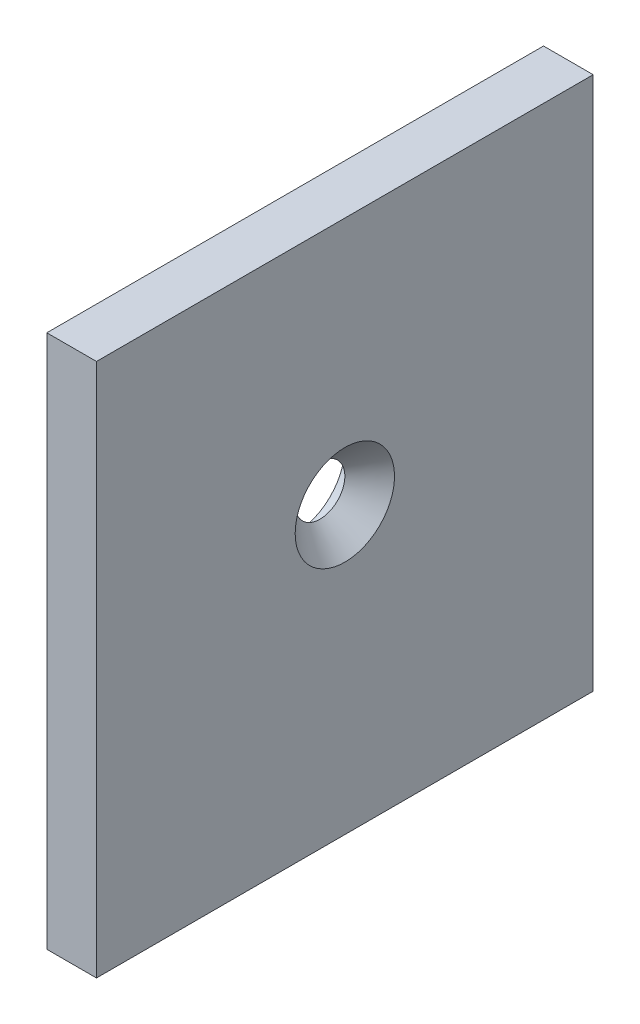
SolidWorks part; units mm, degrees
ref_plane "Plan de face" through (0, 0, 0) normal (0, 0, 1) x (1, 0, 0)
ref_plane "Plan de dessus" through (0, 0, 0) normal (0, 1, 0) x (1, 0, 0)
ref_plane "Plan de droite" through (0, 0, 0) normal (1, 0, 0) x (0, 0, -1)
sketch "Esquisse1" plane through (0, 0, 0) normal (0, 0, 1) x (1, 0, 0)
  line L0 (0, 0) -> (0, 43)
  line L1 (4, 0) -> (4, 43)
  line L2 (0, 0) -> (4, 0)
  line L3 (4, 43) -> (0, 43)
  dimension "D1" = 4
extrude "Extrusion1" add sketch "Esquisse1" along normal blind 40
sketch "Esquisse2" plane through (0, 0, 0) normal (-1, 0, 0) x (0, 0, 1)
  line L2 (40, 0) -> (0, 0) construction
  circle A1 centre (20, 23) radius 2
  dimension "D1" = 23
extrude "Extrusion2" cut sketch "Esquisse2" against normal through all
sketch "Esquisse4" plane through (0, 0, 0) normal (-1, 0, 0) x (0, 0, 1)
  circle A0 centre (20, 23) radius 4
extrude "Extrusion3" cut sketch "Esquisse4" against normal blind 2
chamfer "Chanfrein1" distance 2 angle 45 1 edges at (4, 23, 22)
